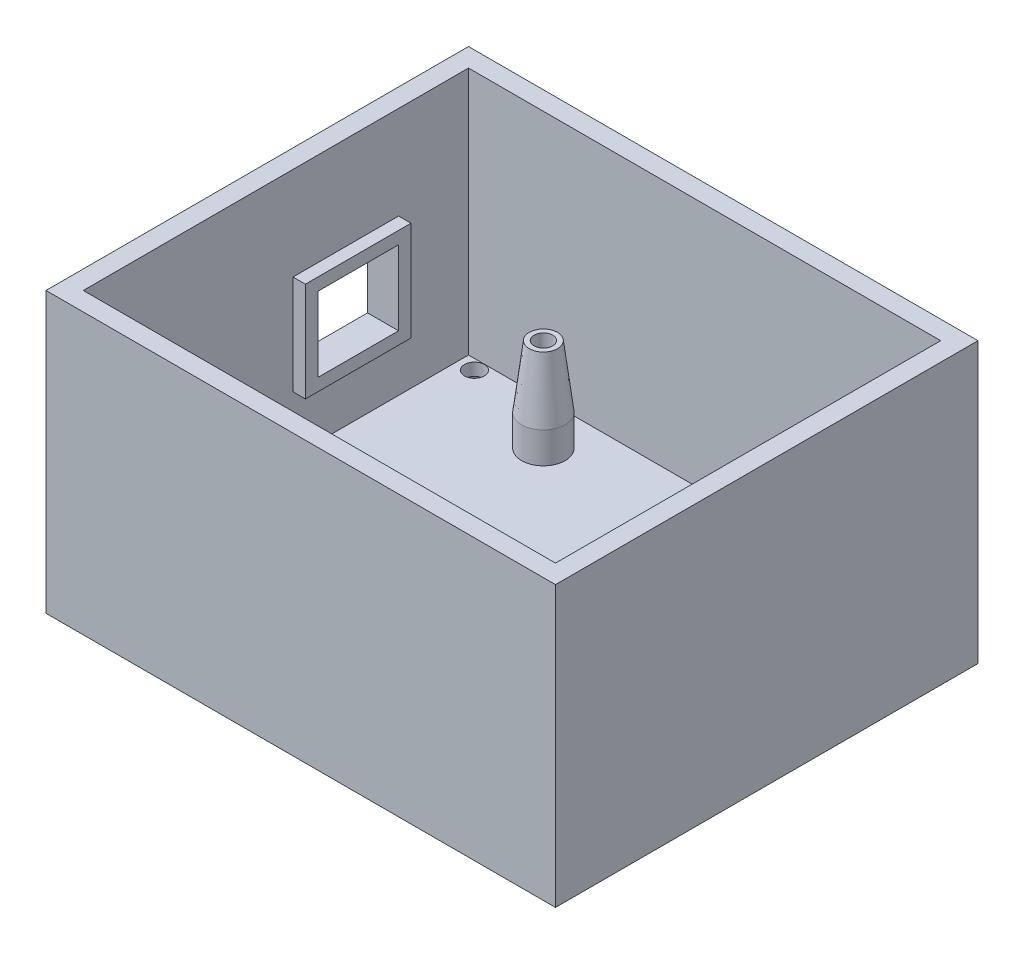
SolidWorks part; units mm, degrees
ref_plane "Спереди" through (0, 0, 0) normal (0, 0, 1) x (1, 0, 0)
ref_plane "Сверху" through (0, 0, 0) normal (0, 1, 0) x (1, 0, 0)
ref_plane "Справа" through (0, 0, 0) normal (1, 0, 0) x (0, 0, -1)
sketch "Sketch1" plane through (0, 0, 0) normal (0, 1, 0) x (1, 0, 0)
  line L1 (41, 34) -> (-41, 34)
  line L2 (41, 34) -> (41, -34)
  line L3 (41, -34) -> (-41, -34)
  line L4 (-41, 34) -> (-41, -34)
  line L5 (41, 34) -> (-41, -34) construction
  line L6 (41, -34) -> (-41, 34) construction
  point P0 (0, 0)
  dimension "D1" = 82
  dimension "D2" = 68
extrude "Boss-Extrude1" add sketch "Sketch1" along normal blind 5
sketch "Sketch2" plane through (0, 5, 0) normal (0, 1, 0) x (1, 0, 0)
  line L1 (-41, 34) -> (41, 34)
  line L2 (-41, 34) -> (-41, -34)
  line L3 (-41, -34) -> (41, -34)
  line L4 (41, 34) -> (41, -34)
  line L5 (-41, 34) -> (41, -34) construction
  line L6 (-41, -34) -> (41, 34) construction
  line L7 (-38, 31) -> (38, 31)
  line L8 (-38, 31) -> (-38, -31)
  line L9 (-38, -31) -> (38, -31)
  line L10 (38, 31) -> (38, -31)
  line L11 (-38, 31) -> (38, -31) construction
  line L12 (-38, -31) -> (38, 31) construction
  point P0 (0, 0)
  point P7 (0, 0)
  dimension "D1" = 3
  dimension "D2" = 3
  dimension "D3" = 76
  dimension "D4" = 62
  dimension "D5" = 82
  dimension "D6" = 68
extrude "Boss-Extrude2" add sketch "Sketch2" along normal blind 40
sketch "Эскиз1" plane through (0, 5, 0) normal (0, 1, 0) x (1, 0, 0)
  line L0 (-34.3, 26.65) -> (34.3, 26.65) construction
  line L1 (34.3, -26.65) -> (-34.3, 26.65) construction
  line L2 (-34.3, -26.65) -> (34.3, 26.65) construction
  line L5 (31.8, -24.15) -> (-34.3, -24.15) construction
  line L7 (34.3, 26.65) -> (34.3, -26.65) construction
  line L8 (34.3, -26.65) -> (-34.3, -26.65) construction
  line L9 (-34.3, -26.65) -> (-34.3, 26.65) construction
  line L10 (-34.3, 26.65) -> (-20.3, 26.65) construction
  line L11 (31.8, 26.65) -> (31.8, 8.85) construction
  line L12 (31.8, 8.85) -> (31.8, 24.05) construction
  line L13 (-20.3, 26.65) -> (-19, 26.65) construction
  line L14 (-20.3, 26.65) -> (-20.3, -26.65) construction
  line L15 (-19, 26.65) -> (31.8, 26.65) construction
  line L16 (31.8, 26.65) -> (31.8, -26.65) construction
  line L17 (31.8, -26.65) -> (31.8, -24.15) construction
  line L18 (31.8, 24.05) -> (-19, 24.05) construction
  line L19 (-19, 26.65) -> (-19, -26.65) construction
  circle A0 centre (31.8, -19.05) radius 1.5
  circle A1 centre (-20.3, -24.15) radius 1.5
  circle A2 centre (31.8, 8.85) radius 1.5
  circle A3 centre (-19, 24.05) radius 1.5
  circle A4 centre (-20.3, -24.15) radius 3.5
  circle A5 centre (-19, 24.05) radius 3.5
  circle A6 centre (31.8, 8.85) radius 3.5
  circle A7 centre (31.8, -19.05) radius 3.5
  point P0 (0, 0)
  point P3 (0, 0)
  point P6 (3.1764, 2.4705)
  point P11 (-20.3, -24.15)
  dimension "D12" = 3
  dimension "D2" = 7
  dimension "D4" = 68.6
  dimension "D5" = 14
  dimension "D6" = 1.3
  dimension "D7" = 50.8
  dimension "D8" = 2.5
  dimension "D9" = 5.1
  dimension "D10" = 27.9
  dimension "D11" = 15.2
extrude "Boss-Extrude3" add sketch "Эскиз1" along normal blind 15
sketch "Sketch4" plane through (-41, 0, 0) normal (-1, 0, 0) x (0, 0, 1)
  line L0 (0, 45) -> (0, 0) construction
  line L1 (-17.75, 28) -> (-4.75, 28)
  line L2 (-17.75, 45) -> (-17.75, 16) construction
  line L3 (-34, 0) -> (34, 0) construction
  line L4 (-4.75, 16) -> (-4.75, 45) construction
  line L5 (26.75, 16) -> (-26.75, 16) construction
  line L6 (-34, 45) -> (34, 45) construction
  line L7 (-17.75, 28) -> (-17.75, 16)
  line L8 (-17.75, 16) -> (-4.75, 16)
  line L10 (-4.75, 16) -> (-4.75, 28)
  point P7 (0, 16)
  point P8 (-11.25, 16)
  dimension "D1" = 53.5
  dimension "D2" = 29
  dimension "D3" = 13
  dimension "D4" = 12
extrude "Cut-Extrude1" cut sketch "Sketch4" against normal up to surface (3 mm away) up to face at (-38, 25, 0)
sketch "Sketch5" plane through (0, 0, 0) normal (0, -1, 0) x (1, 0, 0)
  line L0 (-41, 0) -> (41, 0) construction
  line L1 (-41, -34) -> (-41, 34) construction
  line L2 (41, 34) -> (41, -34) construction
  circle A0 centre (-20, 0) radius 1.6
  circle A1 centre (20, 0) radius 1.6
  dimension "D1" = 40
  dimension "D3" = 3.2
  dimension "D2" = 20
extrude "Cut-Extrude2" cut sketch "Sketch5" against normal through all
sketch "Sketch6" plane through (0, 0, -34) normal (0, 0, -1) x (-1, 0, 0)
  line L0 (-41, 15) -> (41, 15) construction
  line L1 (-41, 45) -> (-41, 0) construction
  line L2 (41, 45) -> (41, 0) construction
  line L3 (-41, 7) -> (41, 7) construction
  line L4 (-41, 0) -> (41, 0) construction
  text T0 "<b>SIMCHAIR MK III</b>" font "Arial Narrow" height 16
  text T1 "<b>I2C EDITION</b>" font "Arial Narrow" height 6
  dimension "D1" = 15
  dimension "D2" = 7
extrude "Boss-Extrude4" add sketch "Sketch6" along normal blind 1
sketch "Sketch7" plane through (0, 0, 0) normal (0, -1, 0) x (1, 0, 0)
  line L0 (-41, -34) -> (41, 34) construction
  line L1 (41, -34) -> (-41, 34) construction
  line L2 (35.4089, -29.3635) -> (-35.4089, -29.3635) construction
  line L3 (-35.4089, -29.3635) -> (-35.4089, 29.3635) construction
  line L4 (-35.4089, 29.3635) -> (35.4089, 29.3635) construction
  line L5 (35.4089, 29.3635) -> (35.4089, -29.3635) construction
  circle A0 centre (35.4089, -29.3635) radius 1.6
  circle A1 centre (-35.4089, -29.3635) radius 1.6
  circle A2 centre (-35.4089, 29.3635) radius 1.6
  circle A3 centre (35.4089, 29.3635) radius 1.6
  dimension "D2" = 3.2
  dimension "D1" = 92
extrude "Cut-Extrude3" cut sketch "Sketch7" against normal through all
sketch "Sketch8" plane through (0, 0, 0) normal (0, -1, 0) x (1, 0, 0)
  line L0 (-41, 34) -> (41, 34) construction
  line L1 (33.8489, 26.6615) -> (36.9689, 26.6615)
  line L2 (36.9689, 26.6615) -> (38.5289, 29.3635)
  line L3 (38.5289, 29.3635) -> (36.9689, 32.0654)
  line L4 (36.9689, 32.0654) -> (33.8489, 32.0654)
  line L5 (33.8489, 32.0654) -> (32.2889, 29.3635)
  line L6 (32.2889, 29.3635) -> (33.8489, 26.6615)
  line L7 (33.8489, -26.6615) -> (32.2889, -29.3635)
  line L8 (32.2889, -29.3635) -> (33.8489, -32.0654)
  line L9 (33.8489, -32.0654) -> (36.9689, -32.0654)
  line L10 (36.9689, -32.0654) -> (38.5289, -29.3635)
  line L11 (38.5289, -29.3635) -> (36.9689, -26.6615)
  line L12 (36.9689, -26.6615) -> (33.8489, -26.6615)
  line L13 (-36.9689, -26.6615) -> (-38.5289, -29.3635)
  line L14 (-38.5289, -29.3635) -> (-36.9689, -32.0654)
  line L15 (-36.9689, -32.0654) -> (-33.8489, -32.0654)
  line L16 (-33.8489, -32.0654) -> (-32.2889, -29.3635)
  line L17 (-32.2889, -29.3635) -> (-33.8489, -26.6615)
  line L18 (-33.8489, -26.6615) -> (-36.9689, -26.6615)
  line L19 (-36.9689, 26.6615) -> (-33.8489, 26.6615)
  line L20 (-33.8489, 26.6615) -> (-32.2889, 29.3635)
  line L21 (-32.2889, 29.3635) -> (-33.8489, 32.0654)
  line L22 (-33.8489, 32.0654) -> (-36.9689, 32.0654)
  line L23 (-36.9689, 32.0654) -> (-38.5289, 29.3635)
  line L24 (-38.5289, 29.3635) -> (-36.9689, 26.6615)
  line L25 (41, -34) -> (-41, -34) construction
  circle A0 centre (35.4089, 29.3635) radius 3.12 construction
  circle A1 centre (35.4089, -29.3635) radius 3.12 construction
  circle A2 centre (-35.4089, -29.3635) radius 3.12 construction
  circle A3 centre (-35.4089, 29.3635) radius 3.12 construction
  dimension "D1" = 6.24
extrude "Cut-Extrude4" cut sketch "Sketch8" against normal blind 3
sketch "Sketch10" plane through (-38, 0, 0) normal (1, 0, 0) x (0, 0, -1)
  line L0 (17.75, 28) -> (4.75, 16) construction
  line L2 (4.75, 16) -> (17.75, 16)
  line L3 (4.75, 16) -> (4.75, 28)
  line L4 (4.75, 28) -> (17.75, 28)
  line L5 (17.75, 16) -> (17.75, 28)
  line L6 (4.75, 16) -> (17.75, 28) construction
  line L7 (4.75, 28) -> (17.75, 16) construction
  line L8 (2.75, 14) -> (19.75, 14)
  line L9 (2.75, 14) -> (2.75, 30)
  line L10 (2.75, 30) -> (19.75, 30)
  line L11 (19.75, 14) -> (19.75, 30)
  line L12 (2.75, 14) -> (19.75, 30) construction
  line L13 (2.75, 30) -> (19.75, 14) construction
  point P4 (11.25, 22)
  point P5 (11.25, 22)
  dimension "D1" = 2
  dimension "D2" = 2
extrude "Boss-Extrude6" add sketch "Sketch10" along normal blind 2
chamfer "Chamfer1" distance 10 angle 7 1 edges at (-19, 20, -20.55) first distance on face at (-19, 20, -20.55)
sketch "Sketch11" plane through (0, 5, 0) normal (0, 1, 0) x (1, 0, 0)
  line L0 (-23.12, 0) -> (23.12, 0) construction
  line L1 (-16.88, 0) -> (-18.44, 2.702)
  line L2 (-18.44, 2.702) -> (-21.56, 2.702)
  line L3 (-21.56, 2.702) -> (-23.12, 0)
  line L4 (-23.12, 0) -> (-21.56, -2.702)
  line L5 (-21.56, -2.702) -> (-18.44, -2.702)
  line L6 (-18.44, -2.702) -> (-16.88, 0)
  line L7 (16.88, 0) -> (18.44, -2.702)
  line L8 (18.44, -2.702) -> (21.56, -2.702)
  line L9 (21.56, -2.702) -> (23.12, 0)
  line L10 (23.12, 0) -> (21.56, 2.702)
  line L11 (21.56, 2.702) -> (18.44, 2.702)
  line L12 (18.44, 2.702) -> (16.88, 0)
  circle A0 centre (-20, 0) radius 3.12 construction
  circle A1 centre (20, 0) radius 3.12 construction
  dimension "D1" = 6.24
extrude "Cut-Extrude5" cut sketch "Sketch11" against normal blind 3
